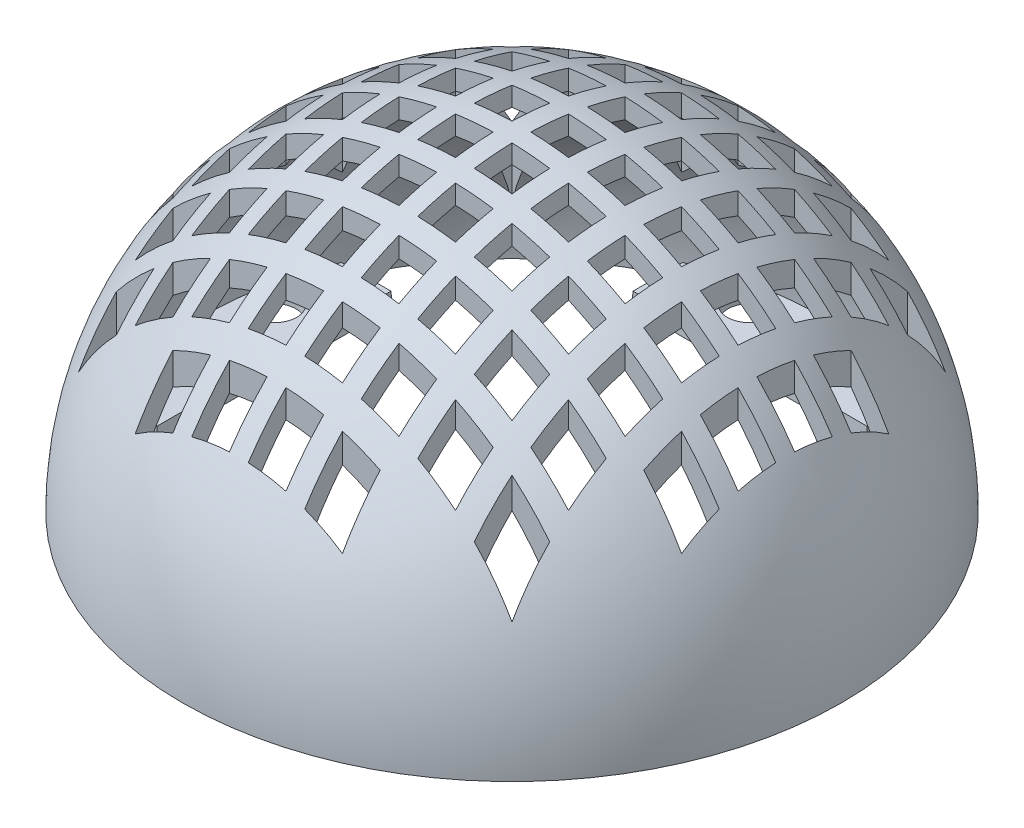
SolidWorks part; units mm, degrees
material "ABS"
ref_plane "Front Plane" through (0, 0, 0) normal (0, 0, 1) x (1, 0, 0)
ref_plane "Top Plane" through (0, 0, 0) normal (0, 1, 0) x (1, 0, 0)
ref_plane "Right Plane" through (0, 0, 0) normal (1, 0, 0) x (0, 0, -1)
sketch "Sketch1" plane through (0, 0, 0) normal (0, 1, 0) x (1, 0, 0)
  line L0 (0, -70) -> (0, 70)
  arc A0 (0, 70) -> (0, -70) centre (0, 0) ccw
  point P4 (0, 0)
  dimension "D1" = 140
sketch "Sketch2" plane through (0, 0, 0) normal (0, 1, 0) x (1, 0, 0)
  line L0 (0, 0) -> (0, 98.853) construction
revolve "Revolve1" add sketch "Sketch1" angle 180 about L0
sketch "Sketch3" plane through (0, 0, 0) normal (0, -1, 0) x (1, 0, 0)
  line L0 (0, -66) -> (0, 66)
  line L2 (0, 0) -> (0, -98.853) construction
  arc A0 (0, 66) -> (0, -66) centre (0, 0) ccw
  point P4 (0, 0)
  dimension "D1" = 132
revolve "Cut-Revolve1" cut sketch "Sketch3" angle 180 about L0
ref_plane "Plane2" through (0, 70, 0) normal (0, 1, 0) x (1, 0, 0)
sketch "Sketch4" plane through (0, 70, 0) normal (0, -1, 0) x (-1, 0, 0)
  line L77 (0, 12.8778) -> (0, -12.8778) construction
  line L94 (-2, 2) -> (-10, 2)
  line L100 (-2, 2) -> (-2, 10)
  line L106 (-2, 10) -> (-10, 10)
  line L112 (-10, 2) -> (-10, 10)
  line L118 (-2, 2) -> (-10, 10) construction
  line L124 (-2, 10) -> (-10, 2) construction
  line L130 (0, 0) -> (0, 98.853) construction
  line L177 (10.4051, 0) -> (-10.4051, 0) construction
  line L178 (-14, 2) -> (-22, 2)
  line L183 (-14, 2) -> (-14, 10)
  line L184 (-14, 10) -> (-22, 10)
  line L189 (-22, 2) -> (-22, 10)
  line L190 (-14, 2) -> (-22, 10) construction
  line L195 (-14, 10) -> (-22, 2) construction
  line L196 (-26, 2) -> (-34, 2)
  line L197 (-26, 2) -> (-26, 10)
  line L198 (-26, 10) -> (-34, 10)
  line L245 (-34, 2) -> (-34, 10)
  line L246 (-26, 2) -> (-34, 10) construction
  line L251 (-26, 10) -> (-34, 2) construction
  line L252 (-38, 2) -> (-46, 2)
  line L257 (-38, 2) -> (-38, 10)
  line L258 (-38, 10) -> (-46, 10)
  line L263 (-46, 2) -> (-46, 10)
  line L264 (-38, 2) -> (-46, 10) construction
  line L312 (-38, 10) -> (-46, 2) construction
  line L313 (-50, 2) -> (-58, 2)
  line L314 (-50, 2) -> (-50, 10)
  line L315 (-50, 10) -> (-58, 10)
  line L316 (-58, 2) -> (-58, 10)
  line L317 (-50, 2) -> (-58, 10) construction
  line L318 (-50, 10) -> (-58, 2) construction
  line L319 (-14, 14) -> (-22, 14)
  line L322 (-14, 14) -> (-14, 22)
  line L323 (-14, 22) -> (-22, 22)
  line L326 (-22, 14) -> (-22, 22)
  line L327 (-14, 14) -> (-22, 22) construction
  line L328 (-14, 22) -> (-22, 14) construction
  line L329 (-26, 14) -> (-34, 14)
  line L330 (-26, 14) -> (-26, 22)
  line L331 (-26, 22) -> (-34, 22)
  line L332 (-34, 14) -> (-34, 22)
  line L333 (-26, 14) -> (-34, 22) construction
  line L334 (-26, 22) -> (-34, 14) construction
  line L335 (-38, 14) -> (-46, 14)
  line L380 (-38, 14) -> (-38, 22)
  line L381 (-38, 22) -> (-46, 22)
  line L382 (-46, 14) -> (-46, 22)
  line L383 (-38, 14) -> (-46, 22) construction
  line L384 (-38, 22) -> (-46, 14) construction
  line L385 (-50, 14) -> (-58, 14)
  line L386 (-50, 14) -> (-50, 22)
  line L387 (-50, 22) -> (-58, 22)
  line L388 (-58, 14) -> (-58, 22)
  line L389 (-50, 14) -> (-58, 22) construction
  line L390 (-50, 22) -> (-58, 14) construction
  line L391 (-14, 26) -> (-22, 26)
  line L392 (-14, 26) -> (-14, 34)
  line L393 (-14, 34) -> (-22, 34)
  line L394 (-22, 26) -> (-22, 34)
  line L395 (-14, 26) -> (-22, 34) construction
  line L396 (-14, 34) -> (-22, 26) construction
  line L397 (-26, 26) -> (-34, 26)
  line L398 (-26, 26) -> (-26, 34)
  line L399 (-26, 34) -> (-34, 34)
  line L400 (-34, 26) -> (-34, 34)
  line L401 (-26, 26) -> (-34, 34) construction
  line L402 (-26, 34) -> (-34, 26) construction
  line L403 (-38, 26) -> (-46, 26)
  line L404 (-38, 26) -> (-38, 34)
  line L405 (-38, 34) -> (-46, 34)
  line L406 (-46, 26) -> (-46, 34)
  line L407 (-38, 26) -> (-46, 34) construction
  line L408 (-38, 34) -> (-46, 26) construction
  line L409 (-50, 26) -> (-58, 26) [skipped]
  line L410 (-50, 26) -> (-50, 34) [skipped]
  line L411 (-50, 34) -> (-58, 34) [skipped]
  line L524 (-58, 26) -> (-58, 34) [skipped]
  line L525 (-50, 26) -> (-58, 34) construction
  line L526 (-50, 34) -> (-58, 26) construction
  line L527 (-14, 38) -> (-22, 38)
  line L528 (-14, 38) -> (-14, 46)
  line L529 (-14, 46) -> (-22, 46)
  line L530 (-22, 38) -> (-22, 46)
  line L531 (-14, 38) -> (-22, 46) construction
  line L532 (-14, 46) -> (-22, 38) construction
  line L533 (-26, 38) -> (-34, 38)
  line L534 (-26, 38) -> (-26, 46)
  line L535 (-26, 46) -> (-34, 46)
  line L536 (-34, 38) -> (-34, 46)
  line L537 (-26, 38) -> (-34, 46) construction
  line L538 (-26, 46) -> (-34, 38) construction
  line L539 (-38, 38) -> (-46, 38)
  line L540 (-38, 38) -> (-38, 46)
  line L541 (-38, 46) -> (-46, 46)
  line L542 (-46, 38) -> (-46, 46)
  line L543 (-38, 38) -> (-46, 46) construction
  line L544 (-38, 46) -> (-46, 38) construction
  line L545 (-50, 38) -> (-58, 38) [skipped]
  line L546 (-50, 38) -> (-50, 46) [skipped]
  line L547 (-50, 46) -> (-58, 46) [skipped]
  line L548 (-58, 38) -> (-58, 46) [skipped]
  line L549 (-50, 38) -> (-58, 46) construction
  line L550 (-50, 46) -> (-58, 38) construction
  line L551 (-14, 50) -> (-22, 50)
  line L552 (-14, 50) -> (-14, 58)
  line L553 (-14, 58) -> (-22, 58)
  line L554 (-22, 50) -> (-22, 58)
  line L555 (-14, 50) -> (-22, 58) construction
  line L556 (-14, 58) -> (-22, 50) construction
  line L557 (-26, 50) -> (-34, 50) [skipped]
  line L558 (-26, 50) -> (-26, 58) [skipped]
  line L559 (-26, 58) -> (-34, 58) [skipped]
  line L560 (-34, 50) -> (-34, 58) [skipped]
  line L561 (-26, 50) -> (-34, 58) construction
  line L562 (-26, 58) -> (-34, 50) construction
  line L563 (-38, 50) -> (-46, 50) [skipped]
  line L564 (-38, 50) -> (-38, 58) [skipped]
  line L565 (-38, 58) -> (-46, 58) [skipped]
  line L566 (-46, 50) -> (-46, 58) [skipped]
  line L567 (-38, 50) -> (-46, 58) construction
  line L568 (-38, 58) -> (-46, 50) construction
  line L569 (-50, 50) -> (-58, 50) [skipped]
  line L570 (-50, 50) -> (-50, 58) [skipped]
  line L571 (-50, 58) -> (-58, 58) [skipped]
  line L572 (-58, 50) -> (-58, 58) [skipped]
  line L573 (-50, 50) -> (-58, 58) construction
  line L574 (-50, 58) -> (-58, 50) construction
  line L575 (-2, 14) -> (-10, 14)
  line L576 (-2, 14) -> (-2, 22)
  line L577 (-2, 22) -> (-10, 22)
  line L578 (-10, 14) -> (-10, 22)
  line L579 (-2, 14) -> (-10, 22) construction
  line L580 (-2, 22) -> (-10, 14) construction
  line L581 (-2, 26) -> (-10, 26)
  line L582 (-2, 26) -> (-2, 34)
  line L583 (-2, 34) -> (-10, 34)
  line L584 (-10, 26) -> (-10, 34)
  line L585 (-2, 26) -> (-10, 34) construction
  line L586 (-2, 34) -> (-10, 26) construction
  line L587 (-2, 38) -> (-10, 38)
  line L588 (-2, 38) -> (-2, 46)
  line L589 (-2, 46) -> (-10, 46)
  line L590 (-10, 38) -> (-10, 46)
  line L591 (-2, 38) -> (-10, 46) construction
  line L592 (-2, 46) -> (-10, 38) construction
  line L593 (-2, 50) -> (-10, 50)
  line L594 (-2, 50) -> (-2, 58)
  line L595 (-2, 58) -> (-10, 58)
  line L596 (-10, 50) -> (-10, 58)
  line L597 (-2, 50) -> (-10, 58) construction
  line L598 (-2, 58) -> (-10, 50) construction
  line L599 (-6, 6) -> (-18, 6) construction
  line L600 (6, 6) -> (18, 6) construction
  line L601 (2, 58) -> (10, 50) construction
  line L602 (2, 50) -> (10, 58) construction
  line L603 (2, 46) -> (10, 38) construction
  line L604 (2, 38) -> (10, 46) construction
  line L605 (2, 34) -> (10, 26) construction
  line L606 (2, 26) -> (10, 34) construction
  line L607 (2, 22) -> (10, 14) construction
  line L608 (2, 14) -> (10, 22) construction
  line L609 (14, 58) -> (22, 50) construction
  line L610 (14, 50) -> (22, 58) construction
  line L611 (38, 46) -> (46, 38) construction
  line L612 (38, 38) -> (46, 46) construction
  line L613 (26, 46) -> (34, 38) construction
  line L614 (26, 38) -> (34, 46) construction
  line L615 (14, 46) -> (22, 38) construction
  line L616 (14, 38) -> (22, 46) construction
  line L617 (38, 34) -> (46, 26) construction
  line L618 (38, 26) -> (46, 34) construction
  line L619 (26, 34) -> (34, 26) construction
  line L620 (26, 26) -> (34, 34) construction
  line L621 (14, 34) -> (22, 26) construction
  line L622 (14, 26) -> (22, 34) construction
  line L623 (50, 22) -> (58, 14) construction
  line L624 (50, 14) -> (58, 22) construction
  line L625 (38, 22) -> (46, 14) construction
  line L626 (38, 14) -> (46, 22) construction
  line L627 (26, 22) -> (34, 14) construction
  line L628 (26, 14) -> (34, 22) construction
  line L629 (14, 22) -> (22, 14) construction
  line L630 (14, 14) -> (22, 22) construction
  line L631 (50, 10) -> (58, 2) construction
  line L632 (50, 2) -> (58, 10) construction
  line L633 (38, 10) -> (46, 2) construction
  line L634 (38, 2) -> (46, 10) construction
  line L635 (26, 10) -> (34, 2) construction
  line L636 (26, 2) -> (34, 10) construction
  line L637 (14, 10) -> (22, 2) construction
  line L638 (14, 2) -> (22, 10) construction
  line L639 (2, 10) -> (10, 2) construction
  line L864 (2, 2) -> (10, 10) construction
  line L865 (10, 50) -> (10, 58)
  line L866 (2, 58) -> (10, 58)
  line L867 (2, 50) -> (2, 58)
  line L868 (2, 50) -> (10, 50)
  line L869 (10, 38) -> (10, 46)
  line L870 (2, 46) -> (10, 46)
  line L871 (2, 38) -> (2, 46)
  line L872 (2, 38) -> (10, 38)
  line L873 (10, 26) -> (10, 34)
  line L874 (2, 34) -> (10, 34)
  line L875 (2, 26) -> (2, 34)
  line L876 (2, 26) -> (10, 26)
  line L877 (10, 14) -> (10, 22)
  line L878 (2, 22) -> (10, 22)
  line L879 (2, 14) -> (2, 22)
  line L880 (2, 14) -> (10, 14)
  line L881 (22, 50) -> (22, 58)
  line L882 (14, 58) -> (22, 58)
  line L883 (14, 50) -> (14, 58)
  line L884 (14, 50) -> (22, 50)
  line L885 (46, 38) -> (46, 46)
  line L886 (38, 46) -> (46, 46)
  line L887 (38, 38) -> (38, 46)
  line L888 (38, 38) -> (46, 38)
  line L889 (34, 38) -> (34, 46)
  line L890 (26, 46) -> (34, 46)
  line L891 (26, 38) -> (26, 46)
  line L892 (26, 38) -> (34, 38)
  line L893 (22, 38) -> (22, 46)
  line L894 (14, 46) -> (22, 46)
  line L895 (14, 38) -> (14, 46)
  line L896 (14, 38) -> (22, 38)
  line L897 (46, 26) -> (46, 34)
  line L898 (38, 34) -> (46, 34)
  line L899 (38, 26) -> (38, 34)
  line L900 (38, 26) -> (46, 26)
  line L901 (34, 26) -> (34, 34)
  line L902 (26, 34) -> (34, 34)
  line L903 (26, 26) -> (26, 34)
  line L904 (26, 26) -> (34, 26)
  line L905 (22, 26) -> (22, 34)
  line L906 (14, 34) -> (22, 34)
  line L907 (14, 26) -> (14, 34)
  line L908 (14, 26) -> (22, 26)
  line L909 (58, 14) -> (58, 22)
  line L910 (50, 22) -> (58, 22)
  line L911 (50, 14) -> (50, 22)
  line L912 (50, 14) -> (58, 14)
  line L913 (46, 14) -> (46, 22)
  line L914 (38, 22) -> (46, 22)
  line L915 (38, 14) -> (38, 22)
  line L916 (38, 14) -> (46, 14)
  line L917 (34, 14) -> (34, 22)
  line L918 (26, 22) -> (34, 22)
  line L919 (26, 14) -> (26, 22)
  line L920 (26, 14) -> (34, 14)
  line L921 (22, 14) -> (22, 22)
  line L922 (14, 22) -> (22, 22)
  line L923 (14, 14) -> (14, 22)
  line L924 (14, 14) -> (22, 14)
  line L925 (58, 2) -> (58, 10)
  line L926 (50, 10) -> (58, 10)
  line L927 (50, 2) -> (50, 10)
  line L928 (50, 2) -> (58, 2)
  line L929 (46, 2) -> (46, 10)
  line L930 (38, 10) -> (46, 10)
  line L931 (38, 2) -> (38, 10)
  line L932 (38, 2) -> (46, 2)
  line L933 (34, 2) -> (34, 10)
  line L934 (26, 10) -> (34, 10)
  line L935 (26, 2) -> (26, 10)
  line L936 (26, 2) -> (34, 2)
  line L937 (22, 2) -> (22, 10)
  line L938 (14, 10) -> (22, 10)
  line L939 (14, 2) -> (14, 10)
  line L940 (14, 2) -> (22, 2)
  line L941 (10, 2) -> (10, 10)
  line L942 (2, 10) -> (10, 10)
  line L943 (2, 2) -> (2, 10)
  line L944 (2, 2) -> (10, 2)
  line L945 (2, -2) -> (10, -10) construction
  line L946 (2, -10) -> (10, -2) construction
  line L947 (14, -2) -> (22, -10) construction
  line L948 (14, -10) -> (22, -2) construction
  line L949 (26, -2) -> (34, -10) construction
  line L950 (26, -10) -> (34, -2) construction
  line L951 (38, -2) -> (46, -10) construction
  line L952 (38, -10) -> (46, -2) construction
  line L953 (50, -2) -> (58, -10) construction
  line L954 (50, -10) -> (58, -2) construction
  line L955 (14, -14) -> (22, -22) construction
  line L956 (14, -22) -> (22, -14) construction
  line L957 (26, -14) -> (34, -22) construction
  line L958 (26, -22) -> (34, -14) construction
  line L959 (38, -14) -> (46, -22) construction
  line L960 (38, -22) -> (46, -14) construction
  line L961 (50, -14) -> (58, -22) construction
  line L962 (50, -22) -> (58, -14) construction
  line L963 (14, -26) -> (22, -34) construction
  line L964 (14, -34) -> (22, -26) construction
  line L965 (26, -26) -> (34, -34) construction
  line L966 (26, -34) -> (34, -26) construction
  line L967 (38, -26) -> (46, -34) construction
  line L968 (38, -34) -> (46, -26) construction
  line L969 (14, -38) -> (22, -46) construction
  line L970 (14, -46) -> (22, -38) construction
  line L971 (26, -38) -> (34, -46) construction
  line L972 (26, -46) -> (34, -38) construction
  line L973 (38, -38) -> (46, -46) construction
  line L974 (38, -46) -> (46, -38) construction
  line L975 (14, -50) -> (22, -58) construction
  line L976 (14, -58) -> (22, -50) construction
  line L977 (2, -14) -> (10, -22) construction
  line L978 (2, -22) -> (10, -14) construction
  line L979 (2, -26) -> (10, -34) construction
  line L980 (2, -34) -> (10, -26) construction
  line L981 (2, -38) -> (10, -46) construction
  line L982 (2, -46) -> (10, -38) construction
  line L983 (2, -50) -> (10, -58) construction
  line L984 (2, -58) -> (10, -50) construction
  line L985 (6, -6) -> (18, -6) construction
  line L986 (-6, -6) -> (-18, -6) construction
  line L987 (-2, -58) -> (-10, -50) construction
  line L988 (-2, -50) -> (-10, -58) construction
  line L989 (-2, -46) -> (-10, -38) construction
  line L990 (-2, -38) -> (-10, -46) construction
  line L991 (-2, -34) -> (-10, -26) construction
  line L992 (-2, -26) -> (-10, -34) construction
  line L993 (-2, -22) -> (-10, -14) construction
  line L994 (-2, -14) -> (-10, -22) construction
  line L995 (-14, -58) -> (-22, -50) construction
  line L996 (-14, -50) -> (-22, -58) construction
  line L997 (-38, -46) -> (-46, -38) construction
  line L998 (-38, -38) -> (-46, -46) construction
  line L999 (-26, -46) -> (-34, -38) construction
  line L1000 (-26, -38) -> (-34, -46) construction
  line L1001 (-14, -46) -> (-22, -38) construction
  line L1002 (-14, -38) -> (-22, -46) construction
  line L1003 (-38, -34) -> (-46, -26) construction
  line L1004 (-38, -26) -> (-46, -34) construction
  line L1005 (-26, -34) -> (-34, -26) construction
  line L1006 (-26, -26) -> (-34, -34) construction
  line L1007 (-14, -34) -> (-22, -26) construction
  line L1008 (-14, -26) -> (-22, -34) construction
  line L1009 (-50, -22) -> (-58, -14) construction
  line L1010 (-50, -14) -> (-58, -22) construction
  line L1011 (-38, -22) -> (-46, -14) construction
  line L1012 (-38, -14) -> (-46, -22) construction
  line L1013 (-26, -22) -> (-34, -14) construction
  line L1014 (-26, -14) -> (-34, -22) construction
  line L1015 (-14, -22) -> (-22, -14) construction
  line L1016 (-14, -14) -> (-22, -22) construction
  line L1017 (-50, -10) -> (-58, -2) construction
  line L1018 (-50, -2) -> (-58, -10) construction
  line L1019 (-38, -10) -> (-46, -2) construction
  line L1020 (-38, -2) -> (-46, -10) construction
  line L1021 (-26, -10) -> (-34, -2) construction
  line L1022 (-26, -2) -> (-34, -10) construction
  line L1023 (-14, -10) -> (-22, -2) construction
  line L1024 (-14, -2) -> (-22, -10) construction
  line L1025 (-2, -10) -> (-10, -2) construction
  line L1026 (-2, -2) -> (-10, -10) construction
  line L1027 (2, -2) -> (10, -2)
  line L1028 (2, -2) -> (2, -10)
  line L1029 (2, -10) -> (10, -10)
  line L1030 (10, -2) -> (10, -10)
  line L1031 (14, -2) -> (22, -2)
  line L1032 (14, -2) -> (14, -10)
  line L1033 (14, -10) -> (22, -10)
  line L1034 (22, -2) -> (22, -10)
  line L1035 (26, -2) -> (34, -2)
  line L1036 (26, -2) -> (26, -10)
  line L1037 (26, -10) -> (34, -10)
  line L1038 (34, -2) -> (34, -10)
  line L1039 (38, -2) -> (46, -2)
  line L1040 (38, -2) -> (38, -10)
  line L1041 (38, -10) -> (46, -10)
  line L1042 (46, -2) -> (46, -10)
  line L1043 (50, -2) -> (58, -2)
  line L1044 (50, -2) -> (50, -10)
  line L1045 (50, -10) -> (58, -10)
  line L1046 (58, -2) -> (58, -10)
  line L1047 (14, -14) -> (22, -14)
  line L1048 (14, -14) -> (14, -22)
  line L1049 (14, -22) -> (22, -22)
  line L1050 (22, -14) -> (22, -22)
  line L1051 (26, -14) -> (34, -14)
  line L1052 (26, -14) -> (26, -22)
  line L1053 (26, -22) -> (34, -22)
  line L1054 (34, -14) -> (34, -22)
  line L1055 (38, -14) -> (46, -14)
  line L1056 (38, -14) -> (38, -22)
  line L1057 (38, -22) -> (46, -22)
  line L1058 (46, -14) -> (46, -22)
  line L1059 (50, -14) -> (58, -14)
  line L1060 (50, -14) -> (50, -22)
  line L1061 (50, -22) -> (58, -22)
  line L1062 (58, -14) -> (58, -22)
  line L1063 (14, -26) -> (22, -26)
  line L1064 (14, -26) -> (14, -34)
  line L1065 (14, -34) -> (22, -34)
  line L1066 (22, -26) -> (22, -34)
  line L1067 (26, -26) -> (34, -26)
  line L1068 (26, -26) -> (26, -34)
  line L1069 (26, -34) -> (34, -34)
  line L1070 (34, -26) -> (34, -34)
  line L1071 (38, -26) -> (46, -26)
  line L1072 (38, -26) -> (38, -34)
  line L1073 (38, -34) -> (46, -34)
  line L1074 (46, -26) -> (46, -34)
  line L1075 (14, -38) -> (22, -38)
  line L1076 (14, -38) -> (14, -46)
  line L1077 (14, -46) -> (22, -46)
  line L1078 (22, -38) -> (22, -46)
  line L1079 (26, -38) -> (34, -38)
  line L1080 (26, -38) -> (26, -46)
  line L1081 (26, -46) -> (34, -46)
  line L1082 (34, -38) -> (34, -46)
  line L1083 (38, -38) -> (46, -38)
  line L1084 (38, -38) -> (38, -46)
  line L1085 (38, -46) -> (46, -46)
  line L1086 (46, -38) -> (46, -46)
  line L1087 (14, -50) -> (22, -50)
  line L1088 (14, -50) -> (14, -58)
  line L1089 (14, -58) -> (22, -58)
  line L1090 (22, -50) -> (22, -58)
  line L1091 (2, -14) -> (10, -14)
  line L1092 (2, -14) -> (2, -22)
  line L1093 (2, -22) -> (10, -22)
  line L1094 (10, -14) -> (10, -22)
  line L1095 (2, -26) -> (10, -26)
  line L1096 (2, -26) -> (2, -34)
  line L1097 (2, -34) -> (10, -34)
  line L1098 (10, -26) -> (10, -34)
  line L1099 (2, -38) -> (10, -38)
  line L1100 (2, -38) -> (2, -46)
  line L1101 (2, -46) -> (10, -46)
  line L1102 (10, -38) -> (10, -46)
  line L1103 (2, -50) -> (10, -50)
  line L1104 (2, -50) -> (2, -58)
  line L1105 (2, -58) -> (10, -58)
  line L1106 (10, -50) -> (10, -58)
  line L1107 (-10, -50) -> (-10, -58)
  line L1108 (-2, -58) -> (-10, -58)
  line L1109 (-2, -50) -> (-2, -58)
  line L1110 (-2, -50) -> (-10, -50)
  line L1111 (-10, -38) -> (-10, -46)
  line L1112 (-2, -46) -> (-10, -46)
  line L1113 (-2, -38) -> (-2, -46)
  line L1114 (-2, -38) -> (-10, -38)
  line L1115 (-10, -26) -> (-10, -34)
  line L1116 (-2, -34) -> (-10, -34)
  line L1117 (-2, -26) -> (-2, -34)
  line L1118 (-2, -26) -> (-10, -26)
  line L1119 (-10, -14) -> (-10, -22)
  line L1120 (-2, -22) -> (-10, -22)
  line L1121 (-2, -14) -> (-2, -22)
  line L1122 (-2, -14) -> (-10, -14)
  line L1123 (-22, -50) -> (-22, -58)
  line L1124 (-14, -58) -> (-22, -58)
  line L1125 (-14, -50) -> (-14, -58)
  line L1126 (-14, -50) -> (-22, -50)
  line L1127 (-46, -38) -> (-46, -46)
  line L1128 (-38, -46) -> (-46, -46)
  line L1129 (-38, -38) -> (-38, -46)
  line L1130 (-38, -38) -> (-46, -38)
  line L1131 (-34, -38) -> (-34, -46)
  line L1132 (-26, -46) -> (-34, -46)
  line L1133 (-26, -38) -> (-26, -46)
  line L1134 (-26, -38) -> (-34, -38)
  line L1135 (-22, -38) -> (-22, -46)
  line L1136 (-14, -46) -> (-22, -46)
  line L1137 (-14, -38) -> (-14, -46)
  line L1138 (-14, -38) -> (-22, -38)
  line L1139 (-46, -26) -> (-46, -34)
  line L1140 (-38, -34) -> (-46, -34)
  line L1141 (-38, -26) -> (-38, -34)
  line L1142 (-38, -26) -> (-46, -26)
  line L1143 (-34, -26) -> (-34, -34)
  line L1144 (-26, -34) -> (-34, -34)
  line L1145 (-26, -26) -> (-26, -34)
  line L1146 (-26, -26) -> (-34, -26)
  line L1147 (-22, -26) -> (-22, -34)
  line L1148 (-14, -34) -> (-22, -34)
  line L1149 (-14, -26) -> (-14, -34)
  line L1150 (-14, -26) -> (-22, -26)
  line L1151 (-58, -14) -> (-58, -22)
  line L1152 (-50, -22) -> (-58, -22)
  line L1153 (-50, -14) -> (-50, -22)
  line L1154 (-50, -14) -> (-58, -14)
  line L1155 (-46, -14) -> (-46, -22)
  line L1156 (-38, -22) -> (-46, -22)
  line L1157 (-38, -14) -> (-38, -22)
  line L1158 (-38, -14) -> (-46, -14)
  line L1159 (-34, -14) -> (-34, -22)
  line L1160 (-26, -22) -> (-34, -22)
  line L1161 (-26, -14) -> (-26, -22)
  line L1162 (-26, -14) -> (-34, -14)
  line L1163 (-22, -14) -> (-22, -22)
  line L1164 (-14, -22) -> (-22, -22)
  line L1165 (-14, -14) -> (-14, -22)
  line L1166 (-14, -14) -> (-22, -14)
  line L1167 (-58, -2) -> (-58, -10)
  line L1168 (-50, -10) -> (-58, -10)
  line L1169 (-50, -2) -> (-50, -10)
  line L1170 (-50, -2) -> (-58, -2)
  line L1171 (-46, -2) -> (-46, -10)
  line L1172 (-38, -10) -> (-46, -10)
  line L1173 (-38, -2) -> (-38, -10)
  line L1174 (-38, -2) -> (-46, -2)
  line L1175 (-34, -2) -> (-34, -10)
  line L1176 (-26, -10) -> (-34, -10)
  line L1177 (-26, -2) -> (-26, -10)
  line L1178 (-26, -2) -> (-34, -2)
  line L1179 (-22, -2) -> (-22, -10)
  line L1180 (-14, -10) -> (-22, -10)
  line L1181 (-14, -2) -> (-14, -10)
  line L1182 (-14, -2) -> (-22, -2)
  line L1183 (-10, -2) -> (-10, -10)
  line L1184 (-2, -10) -> (-10, -10)
  line L1185 (-2, -2) -> (-2, -10)
  line L1186 (-2, -2) -> (-10, -2)
  point P0 (-6, 6)
  point P6 (6, -6)
  point P13 (-18, 6)
  point P18 (-30, 6)
  point P23 (-42, 6)
  point P28 (-54, 6)
  point P33 (-18, 18)
  point P38 (-30, 18)
  point P43 (-42, 18)
  point P48 (-54, 18)
  point P53 (-18, 30)
  point P58 (-30, 30)
  point P63 (-42, 30)
  point P68 (-54, 30)
  point P73 (-18, 42)
  point P78 (-30, 42)
  point P83 (-42, 42)
  point P88 (-54, 42)
  point P93 (-18, 54)
  point P98 (-30, 54)
  point P103 (-42, 54)
  point P108 (-54, 54)
  point P113 (-6, 18)
  point P118 (-6, 30)
  point P123 (-6, 42)
  point P128 (-6, 54)
  point P215 (6, 54)
  point P216 (6, 42)
  point P217 (6, 30)
  point P218 (6, 18)
  point P219 (18, 54)
  point P220 (42, 42)
  point P221 (30, 42)
  point P222 (18, 42)
  point P223 (42, 30)
  point P224 (30, 30)
  point P225 (18, 30)
  point P226 (54, 18)
  point P227 (42, 18)
  point P228 (30, 18)
  point P229 (18, 18)
  point P230 (54, 6)
  point P231 (42, 6)
  point P232 (30, 6)
  point P233 (18, 6)
  point P234 (6, 6)
  point P409 (0, 0)
  point P410 (18, -6)
  point P411 (30, -6)
  point P412 (42, -6)
  point P413 (54, -6)
  point P414 (18, -18)
  point P415 (30, -18)
  point P416 (42, -18)
  point P417 (54, -18)
  point P418 (18, -30)
  point P419 (30, -30)
  point P420 (42, -30)
  point P421 (18, -42)
  point P422 (30, -42)
  point P423 (42, -42)
  point P424 (18, -54)
  point P425 (6, -18)
  point P426 (6, -30)
  point P427 (6, -42)
  point P428 (6, -54)
  point P429 (-6, -54)
  point P430 (-6, -42)
  point P431 (-6, -30)
  point P432 (-6, -18)
  point P433 (-18, -54)
  point P434 (-42, -42)
  point P435 (-30, -42)
  point P436 (-18, -42)
  point P437 (-42, -30)
  point P438 (-30, -30)
  point P439 (-18, -30)
  point P440 (-54, -18)
  point P441 (-42, -18)
  point P442 (-30, -18)
  point P443 (-18, -18)
  point P444 (-54, -6)
  point P445 (-42, -6)
  point P446 (-30, -6)
  point P447 (-18, -6)
  point P448 (-6, -6)
  dimension "D1" = 8
  dimension "D2" = 8
  dimension "D3" = 2
  dimension "D4" = 2
  dimension "D5" = 12
extrude "Cut-Extrude1" cut sketch "Sketch4" against normal up to surface (4.7926 mm away)
sketch "Sketch5" plane through (0, 0, 0) normal (0, 1, 0) x (1, 0, 0)
  line L3 (-50.3835, -25) -> (-50.3835, 25)
  line L5 (-50.3835, 25) -> (-65.3835, 25)
  line L6 (-50.3835, -25) -> (-65.3835, -25)
  line L7 (-25, 50.3835) -> (25, 50.3835)
  line L8 (25, 50.3835) -> (25, 65.3835)
  line L9 (-25, 50.3835) -> (-25, 65.3835)
  line L10 (50.3835, 25) -> (50.3835, -25)
  line L11 (50.3835, -25) -> (65.3835, -25)
  line L12 (50.3835, 25) -> (65.3835, 25)
  line L13 (25, -50.3835) -> (-25, -50.3835)
  line L14 (-25, -50.3835) -> (-25, -65.3835)
  line L15 (25, -50.3835) -> (25, -65.3835)
  arc A3 (-65.3835, -25) -> (-65.3835, 25) centre (0, 0) cw
  arc A4 (-25, 65.3835) -> (25, 65.3835) centre (0, 0) cw
  arc A5 (65.3835, 25) -> (65.3835, -25) centre (0, 0) cw
  arc A6 (25, -65.3835) -> (-25, -65.3835) centre (0, 0) cw
  circle A7 centre (-60.3835, -10) radius 4.5
  circle A8 centre (-60.3835, 10) radius 4.5
  circle A9 centre (-10, 60.3835) radius 4.5
  circle A10 centre (10, 60.3835) radius 4.5
  circle A11 centre (60.3835, 10) radius 4.5
  circle A12 centre (60.3835, -10) radius 4.5
  circle A13 centre (10, -60.3835) radius 4.5
  circle A14 centre (-10, -60.3835) radius 4.5
  point P4 (-50.3835, 0)
  point P13 (0, 50.3835)
  point P20 (50.3835, 0)
  point P25 (0, -50.3835)
  dimension "D4" = 9
  dimension "D5" = 9
  dimension "D8" = 10
  dimension "D9" = 120.767
  dimension "D1" = 50
  dimension "D2" = 15
  dimension "D6" = 10
  dimension "D7" = 10
  dimension "D3" = 4
extrude "Boss-Extrude1" add sketch "Sketch5" along normal blind 3 draft 3
